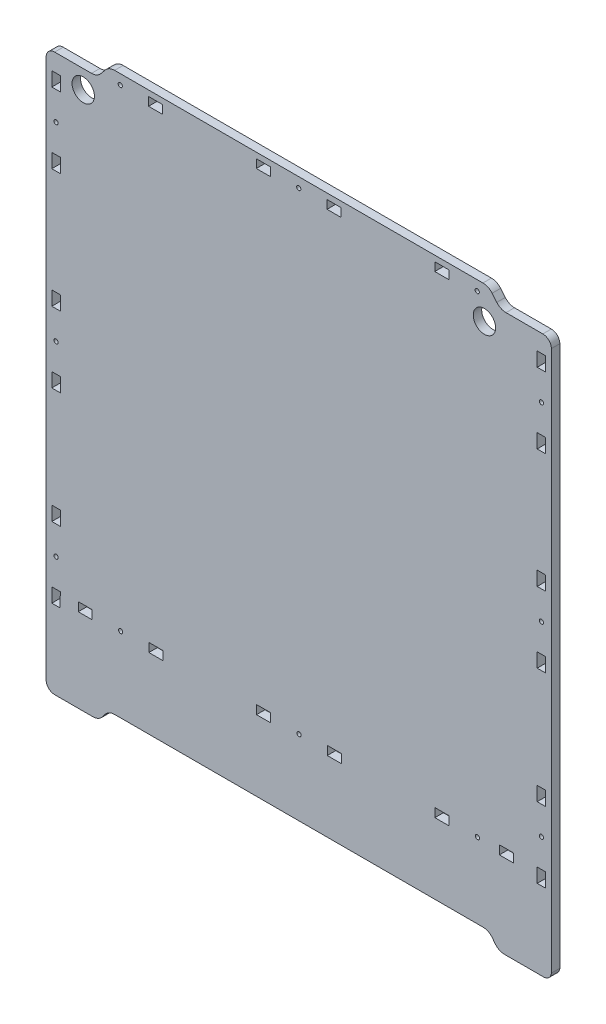
SolidWorks part; units mm, degrees
ref_plane "Спереди" through (0, 0, 0) normal (0, 0, 1) x (1, 0, 0)
ref_plane "Сверху" through (0, 0, 0) normal (0, 1, 0) x (1, 0, 0)
ref_plane "Справа" through (0, 0, 0) normal (1, 0, 0) x (0, 0, -1)
sketch "Эскиз1" plane through (0, 0, 0) normal (0, 0, 1) x (1, 0, 0)
  line L0 (146.8614, 191.5323) -> (172.8978, 191.5323)
  line L1 (-168.1022, 44.9723) -> (-168.1022, 34.9723)
  line L2 (174.8978, 34.9723) -> (168.8978, 34.9723)
  line L3 (178.8978, 185.543) -> (178.8978, -196.6758)
  line L4 (-178.1022, 185.543) -> (-178.1022, -195.7677)
  line L5 (172.8978, -201.7677) -> (145.8614, -201.7677)
  line L6 (-138.5545, -198.7314) -> (-136.2586, -195.7117)
  line L7 (-172.1022, -201.7677) -> (-145.0658, -201.7677)
  line L8 (-129.7473, -192.6754) -> (130.5428, -192.6754)
  line L9 (139.35, -198.7314) -> (137.0542, -195.7117)
  line L10 (174.8978, 179.1323) -> (174.8978, 169.359)
  line L11 (96.5378, 197.5323) -> (106.4199, 197.5323)
  line L12 (106.4199, 197.5323) -> (106.5378, 197.5149)
  line L13 (174.8978, 169.359) -> (174.8978, 169.1323)
  line L14 (137.0542, 198.496) -> (140.35, 194.5682)
  line L15 (130.5428, 201.5323) -> (-129.7473, 201.5323)
  line L16 (-136.2586, 198.4964) -> (-139.5545, 194.5686)
  line L17 (-146.0658, 191.5323) -> (-172.1022, 191.5323)
  line L18 (106.4199, 191.5323) -> (96.5378, 191.5323)
  line L19 (-168.1022, 34.9723) -> (-174.1022, 34.9723)
  line L20 (30.5209, -142.6754) -> (20.5466, -142.6754)
  line L21 (168.8978, 34.9723) -> (168.8978, 44.9723)
  line L22 (30.5209, -136.4756) -> (30.5209, -142.6754)
  line L23 (-29.4488, -136.4756) -> (-19.4791, -136.4756)
  line L24 (20.5466, -142.6754) -> (20.5466, -136.4756)
  line L25 (-19.4791, -142.6754) -> (-29.4488, -142.6754)
  line L26 (-19.4791, -136.4756) -> (-19.4791, -142.6754)
  line L27 (-168.1022, 179.1323) -> (-168.1022, 169.1323)
  line L28 (-29.4488, -142.6754) -> (-29.4488, -136.4756)
  line L29 (-174.1022, 34.9723) -> (-174.1022, 44.9723)
  line L30 (-174.1022, 44.9723) -> (-168.1022, 44.9723)
  line L31 (20.5466, -136.4756) -> (30.5209, -136.4756)
  line L32 (-174.1022, 179.1323) -> (-168.1022, 179.1323)
  line L33 (106.6155, -142.6768) -> (96.6207, -142.6768)
  line L34 (96.6207, -142.6768) -> (96.6207, -136.477)
  line L35 (96.6207, -136.477) -> (106.6155, -136.477)
  line L36 (106.6155, -136.477) -> (106.6155, -142.6768)
  line L37 (152.0021, -142.6768) -> (142.1529, -142.6768)
  line L38 (142.1529, -142.6768) -> (142.1529, -136.477)
  line L39 (142.1529, -136.477) -> (152.0021, -136.477)
  line L40 (152.0021, -136.477) -> (152.0021, -142.6768)
  line L41 (-19.5916, 191.5323) -> (-29.5916, 191.5323)
  line L42 (-29.5916, 191.5323) -> (-29.5928, 197.5323)
  line L43 (-29.5928, 197.5323) -> (-19.5928, 197.5323)
  line L44 (-19.5928, 197.5323) -> (-19.5916, 191.5323)
  line L45 (-174.1022, 119.1323) -> (-174.1022, 129.1323)
  line L46 (-145.5736, -136.477) -> (-145.5736, -142.6768)
  line L47 (-155.4227, -136.477) -> (-145.5736, -136.477)
  line L48 (20.3878, 197.5323) -> (30.3878, 197.5323)
  line L49 (30.3878, 197.5323) -> (30.3878, 191.5323)
  line L50 (-145.5736, -142.6768) -> (-155.4227, -142.6768)
  line L51 (-174.1022, -5.0277) -> (-168.1022, -5.0277)
  line L52 (-174.1022, -15.0277) -> (-174.1022, -5.0277)
  line L53 (-174.1022, 169.1323) -> (-174.1022, 179.1323)
  line L54 (-168.1022, -5.0277) -> (-168.1022, -15.0277)
  line L55 (30.3878, 191.5323) -> (20.3878, 191.5323)
  line L56 (-155.4227, -142.6768) -> (-155.4227, -136.477)
  line L57 (-168.1022, 119.1323) -> (-174.1022, 119.1323)
  line L58 (-168.1022, -15.0277) -> (-174.1022, -15.0277)
  line L59 (20.3878, 191.5323) -> (20.3878, 197.5323)
  line L60 (-168.1022, 169.1323) -> (-174.1022, 169.1323)
  line L61 (-174.1022, -86.7577) -> (-168.1022, -86.7577)
  line L62 (-174.1022, -96.7577) -> (-174.1022, -86.7577)
  line L63 (-168.1022, 129.1323) -> (-168.1022, 119.1323)
  line L64 (-174.1022, 129.1323) -> (-168.1022, 129.1323)
  line L65 (-174.1022, -136.7477) -> (-168.1022, -136.7477)
  line L66 (-174.1022, -146.7477) -> (-174.1022, -136.7477)
  line L67 (-105.5235, -142.6768) -> (-105.5235, -136.477)
  line L68 (-105.5235, -136.477) -> (-95.5735, -136.477)
  line L69 (-95.5735, -136.477) -> (-95.5735, -142.6768)
  line L70 (-168.2894, -146.7477) -> (-174.1022, -146.7477)
  line L71 (-168.1022, -136.7477) -> (-168.2894, -146.7477)
  line L72 (-168.1022, -96.7577) -> (-174.1022, -96.7577)
  line L73 (-168.1022, -86.7577) -> (-168.1022, -96.7577)
  line L74 (174.8978, -15.0277) -> (168.8978, -15.0277)
  line L75 (168.8978, -96.7577) -> (168.8978, -86.7577)
  line L76 (174.8978, -5.0277) -> (174.8978, -15.0277)
  line L77 (174.8978, -86.7577) -> (174.8978, -96.7577)
  line L78 (174.8978, -96.7577) -> (168.8978, -96.7577)
  line L79 (168.8978, -146.7477) -> (168.8978, -136.7477)
  line L80 (168.8978, -136.7477) -> (174.8978, -136.7477)
  line L81 (174.8978, -136.7477) -> (174.8978, -146.7477)
  line L82 (168.8978, -86.7577) -> (174.8978, -86.7577)
  line L83 (168.8978, 179.1323) -> (174.8978, 179.1323)
  line L84 (168.8978, 119.1323) -> (168.8978, 129.1323)
  line L85 (168.8978, 129.1323) -> (174.8978, 129.1323)
  line L86 (174.8978, 129.1323) -> (174.8978, 119.1323)
  line L87 (168.8978, 44.9723) -> (174.8978, 44.9723)
  line L88 (174.8978, 169.1323) -> (168.8978, 169.1323)
  line L89 (174.8978, 44.9723) -> (174.8978, 34.9723)
  line L90 (-95.7416, 191.5323) -> (-105.7416, 191.5323)
  line L91 (106.5378, 191.3325) -> (106.4199, 191.5323)
  line L92 (-105.7416, 191.5323) -> (-105.7428, 197.5323)
  line L93 (174.8978, 119.1323) -> (168.8978, 119.1323)
  line L94 (-105.7428, 197.5323) -> (-95.7428, 197.5323)
  line L95 (-95.7428, 197.5323) -> (-95.7416, 191.5323)
  line L96 (174.8978, -146.7477) -> (168.8978, -146.7477)
  line L97 (168.8978, 169.1323) -> (168.8978, 179.1323)
  line L98 (106.5378, 197.5149) -> (106.5378, 191.3325)
  line L99 (-95.5735, -142.6768) -> (-105.5235, -142.6768)
  line L100 (96.5378, 191.5323) -> (96.5378, 197.5323)
  line L101 (168.8978, -15.0277) -> (168.8978, -5.0277)
  line L102 (168.8978, -5.0277) -> (174.8978, -5.0277)
  arc A0 (-172.1022, 191.5323) -> (-178.1022, 185.543) centre (-172.1022, 185.5323) ccw
  circle A1 centre (126.6857, -139.5423) radius 1.5
  circle A2 centre (0.6186, -139.5423) radius 1.5
  circle A3 centre (-125.5067, -139.5423) radius 1.5
  arc A4 (172.8978, -201.7677) -> (178.8978, -196.6758) centre (173.3519, -196.2218) ccw
  arc A5 (-129.7473, -192.6754) -> (-136.2586, -195.7117) centre (-129.7473, -201.1754) ccw
  arc A6 (139.35, -198.7314) -> (145.8614, -201.7677) centre (145.8614, -193.2677) ccw
  arc A7 (-145.0658, -201.7677) -> (-138.5545, -198.7314) centre (-145.0658, -193.2677) ccw
  arc A8 (-178.1022, -195.7677) -> (-172.1022, -201.7677) centre (-172.1022, -195.7677) ccw
  arc A9 (137.0542, -195.7117) -> (130.5428, -192.6754) centre (130.5428, -201.1754) ccw
  arc A10 (178.8978, 185.543) -> (172.8978, 191.5323) centre (172.8978, 185.5323) ccw
  arc A11 (137.0542, 198.496) -> (130.5428, 201.5323) centre (130.5428, 193.0323) ccw
  arc A12 (140.35, 194.5682) -> (146.8614, 191.5323) centre (146.861, 200.0323) ccw
  circle A13 centre (-171.1022, -116.7377) radius 1.5
  circle A14 centre (-171.1022, 14.9723) radius 1.5
  circle A15 centre (171.8978, 149.1323) radius 1.5
  circle A16 centre (126.5378, 194.5323) radius 1.5
  circle A17 centre (-151.9022, 178.5323) radius 7.9
  circle A18 centre (171.8978, -116.7377) radius 1.5
  circle A19 centre (171.8978, 14.9723) radius 1.5
  circle A20 centre (-171.1022, 149.1323) radius 1.5
  circle A21 centre (-125.7422, 194.5323) radius 1.5
  circle A22 centre (0.3978, 194.5444) radius 1.5
  circle A23 centre (131.5978, 178.5323) radius 7.9
  arc A24 (-129.7473, 201.5323) -> (-136.2586, 198.4964) centre (-129.7476, 193.0323) ccw
  arc A25 (-146.0658, 191.5323) -> (-139.5545, 194.5686) centre (-146.0658, 200.0323) ccw
  point P155 (-174.1022, 124.1323)
  point P156 (-171.1958, -146.7477)
  point P157 (106.5378, 194.4237)
  dimension "D1" = 357
  dimension "D2" = 403.3
  dimension "D3" = 403.3
  dimension "D4" = 23
  dimension "D5" = 26.2
  dimension "D6" = 4
  dimension "D7" = 10
  dimension "D8" = 22.4
  dimension "D9" = 10
  dimension "D10" = 7
  dimension "D11" = 20
  dimension "D12" = 20
  dimension "D13" = 10
  dimension "D14" = 74.16
  dimension "D15" = 4
  dimension "D16" = 6
  dimension "D17" = 6
  dimension "D18" = 10
  dimension "D19" = 4
  dimension "D20" = 20
  dimension "D21" = 20
  dimension "D22" = 10
  dimension "D23" = 7
  dimension "D24" = 4
  dimension "D25" = 71.73
  dimension "D26" = 4
  dimension "D27" = 10
  dimension "D28" = 19.98
  dimension "D29" = 7
  dimension "D30" = 20.01
  dimension "D31" = 10
  dimension "D32" = 55.02
  dimension "D33" = 4
  dimension "D34" = 23
  dimension "D35" = 47.3
  dimension "D36" = 10
  dimension "D37" = 12.4
  dimension "D38" = 10
  dimension "D39" = 20
  dimension "D40" = 20
  dimension "D41" = 10
  dimension "D42" = 74.16
  dimension "D43" = 10
  dimension "D44" = 6
  dimension "D45" = 6
  dimension "D46" = 6
  dimension "D47" = 6
  dimension "D48" = 6
  dimension "D49" = 4
  dimension "D50" = 7
  dimension "D51" = 4
  dimension "D52" = 6
  dimension "D53" = 6
  dimension "D54" = 4
  dimension "D55" = 20
  dimension "D56" = 20
  dimension "D57" = 7
  dimension "D58" = 4
  dimension "D59" = 6
  dimension "D60" = 71.73
  dimension "D61" = 4
  dimension "D62" = 6
  dimension "D63" = 7
  dimension "D64" = 19.98
  dimension "D65" = 20.01
  dimension "D66" = 10
  dimension "D67" = 6
  dimension "D68" = 4
  dimension "D69" = 55.02
  dimension "D70" = 7
  dimension "D71" = 4
  dimension "D72" = 4
  dimension "D73" = 4
  dimension "D74" = 7
  dimension "D75" = 4
  dimension "D76" = 6
  dimension "D77" = 10
  dimension "D78" = 6
  dimension "D79" = 10
  dimension "D80" = 10
  dimension "D81" = 6
  dimension "D82" = 6
  dimension "D83" = 10
  dimension "D84" = 52.36
  dimension "D85" = 20
  dimension "D86" = 66.15
  dimension "D87" = 178.5
  dimension "D88" = 19.99
  dimension "D89" = 52.36
  dimension "D90" = 20
  dimension "D91" = 66.15
  dimension "D92" = 19.99
extrude "Бобышка-Вытянуть1" add sketch "Эскиз1" along normal blind 6
